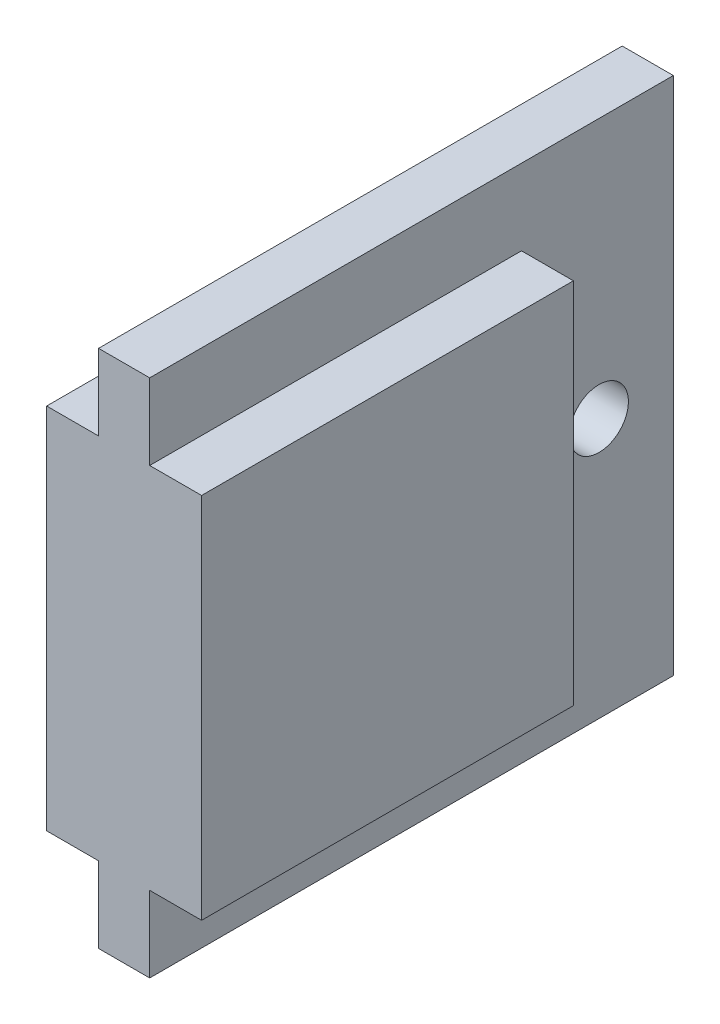
SolidWorks part; units mm, degrees
ref_plane "Front Plane" through (0, 0, 0) normal (1, 0, 0) x (0, 1, 0)
ref_plane "Top Plane" through (0, 0, 0) normal (0, 0, 1) x (0, 1, 0)
ref_plane "Right Plane" through (0, 0, 0) normal (0, 1, 0) x (-1, 0, 0)
sketch "Sketch1" plane through (0, 0, 0) normal (1, 0, 0) x (0, 1, 0)
  line L1 (0, 0) -> (23.75, 0)
  line L2 (0, 0) -> (0, 24)
  line L3 (0, 24) -> (23.75, 24)
  line L4 (23.75, 0) -> (23.75, 24)
  dimension "D1" = 23.75
  dimension "D2" = 24
extrude "Boss-Extrude1" add sketch "Sketch1" against normal blind 10
sketch "Sketch2" plane through (0, 0, 0) normal (0, -1, 0) x (1, 0, 0)
  line L1 (-10, 0) -> (-6.65, 0)
  line L2 (-10, 0) -> (-10, -9.8)
  line L3 (-10, -9.8) -> (-6.65, -9.8)
  line L4 (-6.65, 0) -> (-6.65, -9.8)
  line L5 (0, 0) -> (-3.35, 0)
  line L6 (0, 0) -> (0, -9.8)
  line L7 (0, -9.8) -> (-3.35, -9.8)
  line L8 (-3.35, 0) -> (-3.35, -9.8)
  line L9 (-6.65, -9.8) -> (-3.35, -9.8)
  line L10 (-6.65, -9.8) -> (-6.65, 0)
  line L11 (-6.65, 0) -> (-3.35, 0)
  line L12 (-3.35, -9.8) -> (-3.35, 0)
  line M12 (-10, 0) -> (0, 0)
  dimension "D1" = 9.8
  dimension "D2" = 3.35
  dimension "D3" = 3.35
extrude "Boss-Extrude2" add sketch "Sketch2" against normal through all contours L4 L9 L8 M12 region at (-5, 0, -4.9)
sketch "Sketch3" plane through (0, 0, 0) normal (0, -1, 0) x (1, 0, 0)
  line L0 (-3.35, 20.65) -> (-3.35, 3.35)
  line L1 (0, 24) -> (-10, 24)
  line L2 (0, 24) -> (0, 0)
  line L3 (0, 0) -> (-10, 0)
  line L4 (-10, 24) -> (-10, 0)
  line L5 (-3.35, 3.35) -> (-6.65, 3.35)
  line L6 (-6.65, 20.65) -> (-6.65, 3.35)
  line L7 (-3.35, 20.65) -> (-6.65, 20.65)
  line L9 (-6.65, 20.65) -> (-3.35, 20.65)
  line L10 (-6.65, 20.65) -> (-6.65, 24)
  line L11 (-6.65, 24) -> (-3.35, 24)
  line L12 (-3.35, 20.65) -> (-3.35, 24)
  line L13 (-6.65, 3.35) -> (-3.35, 3.35)
  line L14 (-6.65, 3.35) -> (-6.65, -9.8)
  line L15 (-6.65, -9.8) -> (-3.35, -9.8)
  line L16 (-3.35, 3.35) -> (-3.35, -9.8)
  line M13 (-6.65, 0) -> (-6.65, -9.8)
  line M14 (-6.65, -9.8) -> (-3.35, -9.8)
  line M15 (-3.35, -9.8) -> (-3.35, 0)
  dimension "D1" = 3.35
extrude "Boss-Extrude3" add sketch "Sketch3" along normal blind 4.9 contours L7 L12 L1 L10 | L0 L7 L6 L5 | L16 L5 L14 L3 | L3 M15 M13 M14 region at (-5, 0, 12) region at (-5, 0, 22.325) region at (-5, 0, 1.675) region at (-5, 0, -4.9)
sketch "Sketch4" plane through (-6.65, 0, 0) normal (-1, 0, 0) x (0, -1, 0)
  line L0 (0, 0) -> (-23.75, 0) construction
  line L1 (-11.875, 0) -> (-23.75, 0)
  line L2 (-11.875, 0) -> (-11.875, -5)
  line L3 (-11.875, -5) -> (-23.75, -5)
  line L4 (-23.75, 0) -> (-23.75, -5)
  circle A0 centre (-11.875, -5) radius 1.9
  dimension "D2" = 3.8
extrude "Cut-Extrude1" cut sketch "Sketch4" against normal up to next contours A0
sketch "Sketch5" plane through (0, 23.75, 0) normal (0, 1, 0) x (-1, 0, 0)
  line L0 (3.25, 20.75) -> (3.25, 3.25)
  line L1 (0, 24) -> (10, 24)
  line L2 (0, 24) -> (0, 0)
  line L3 (0, 0) -> (10, 0)
  line L4 (10, 24) -> (10, 0)
  line L5 (3.25, 3.25) -> (6.75, 3.25)
  line L6 (6.75, 20.75) -> (6.75, 3.25)
  line L7 (3.25, 20.75) -> (6.75, 20.75)
  line L9 (3.25, 20.75) -> (6.75, 20.75)
  line L10 (3.25, 20.75) -> (3.25, 24)
  line L11 (3.25, 24) -> (6.75, 24)
  line L12 (6.75, 20.75) -> (6.75, 24)
  dimension "D1" = 3.25
extrude "Cut-Extrude2" [suppressed] cut sketch "Sketch5" against normal blind 5 contours L10 L9 L12 L11 | L0 L5 L6 L7
ref_plane "Plane1" through (0, 11.875, 0) normal (0, -1, 0) x (-1, 0, 0)
mirror "Mirror1" about plane through (0, 11.875, 0) normal (0, -1, 0) of "Boss-Extrude3"
equation "\"whitekey_cutout_length\"= 101.5"
equation "\"key_mount_recess_length\"=50"
equation "\"key_mount_recess_height\"=12.5"
equation "\"key_mount_recess_depth\"=1.5"
equation "\"wall_thickness\"=10"
equation "\"guide_brace_height\"=20"
equation "\"guide_brace_thickness\"=2"
equation "\"dowel_recess_depth\"=10"
equation "\"dowel_recess_offset\"=3.25"
equation "\"base_mount_height\"=40"
equation "\"base_rear_length\"=80"
equation "\"base_front_length\"=111.5"
equation "\"screw_hole_wall_offset\"=7.25"
equation "\"screw_hole_edge_inset\"=\"dowel_recess_depth\"/2"
equation "\"screw_hole_diameter\"=3.8"
equation "\"screw_head_hole_diameter\"=6.7"
equation "\"screw_nut_hole_side_len\"=3.5"
equation "\"screw_shaft_diameter\"=3.5"
equation "\"switch_board_width\"=30"
equation "\"switch_board_wall_offset\"=11.5"
equation "\"heatset_insert_hole_diameter\"=4.8"
equation "\"heatset_insert_hole_depth\"=3.8"
equation "\"D1@Boss-Extrude1\"=\"wall_thickness\""
equation "\"D2@Sketch2\"=\"dowel_recess_offset\"+\"dowel_insert_tolerance\""
equation "\"D3@Sketch2\"=\"dowel_recess_offset\"+\"dowel_insert_tolerance\""
equation "\"D1@Boss-Extrude3\"=\"front_rear_panel_recess_depth\"-\"dowel_insert_tolerance\""
equation "\"D1@Sketch3\"=\"dowel_recess_offset\"+\"dowel_insert_tolerance\""
equation "\"D1@Sketch2\"=\"dowel_recess_depth\"-\"dowel_insert_tolerance\"*2"
equation "\"D1@Sketch4\"=\"screw_hole_edge_inset\""
equation "\"D2@Sketch4\"=\"screw_hole_diameter\""
equation "\"D1@Sketch5\"=\"dowel_recess_offset\""
equation "\"D1@Cut-Extrude2\"=\"front_rear_panel_recess_depth\""
equation "\"screw_nut_recess_offset\"=0.35"
equation "\"screw_head_and_nut_recess_depth\"=2.5"
equation "\"front_rear_panel_width\"=23.75"
equation "\"rod_length_adj\"=0.5"
equation "\"rod_insert_length\"=2.8"
equation "\"D1@Sketch1\"=\"front_rear_panel_width\""
equation "\"switch_board_thickness\"=1.6"
equation "\"front_panel_height\"=24"
equation "\"rod_diameter\"=5"
equation "\"rod_head_diameter\"=8"
equation "\"switch_black_key_mount_height\"=8"
equation "\"switch_white_key_mount_height\"=3"
equation "\"D2@Sketch1\"=\"front_panel_height\""
equation "\"dowel_insert_tolerance\"=0.1"
equation "\"front_rear_panel_recess_depth\"=5"
